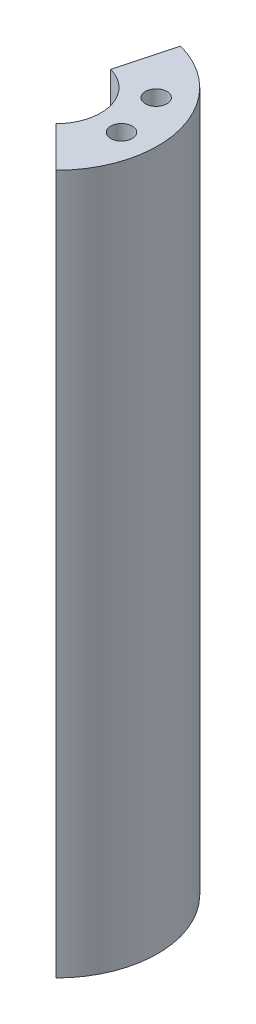
SolidWorks part; units mm, degrees
ref_plane "Front" through (0, 0, 0) normal (0, 0, 1) x (1, 0, 0)
ref_plane "Top" through (0, 0, 0) normal (0, 1, 0) x (1, 0, 0)
ref_plane "Right" through (0, 0, 0) normal (1, 0, 0) x (0, 0, -1)
sketch "Sketch1" plane through (0, 0, 0) normal (0, 1, 0) x (1, 0, 0)
  line L0 (0, 0) -> (-11.3137, 11.3137)
  line L1 (0, 0) -> (11.3137, -11.3137)
  line L2 (0, 0) -> (4.1411, 15.4548)
  line L3 (0, 0) -> (11.2707, -0.9861)
  line L4 (0, 0) -> (9.2676, 6.4893)
  circle A0 centre (0, 0) radius 16
  circle A1 centre (0, 0) radius 7
  circle A2 centre (0, 0) radius 11.3137
  circle A3 centre (0, 11.3137) radius 1.25
  circle A5 centre (11.2707, -0.9861) radius 1.7
  circle A6 centre (9.2676, 6.4893) radius 1.7
  dimension "D1" = 120
  dimension "D2" = 40
  dimension "D3" = 40
extrude "Boss-Extrude1" add sketch "Sketch1" along normal blind 110.3 contours A6 A2 L1 A0 L2 | A6 A2 L2 A1 L1 | A6 L4 A1 L3 A5 A2 | A5 L3 A1 L1 A2 region at (8.0925, 0, 4.0558) region at (4.9804, 0, -7.5587) region at (8.6371, 0, -2.3143) region at (11.0249, 0, -2.9541)
